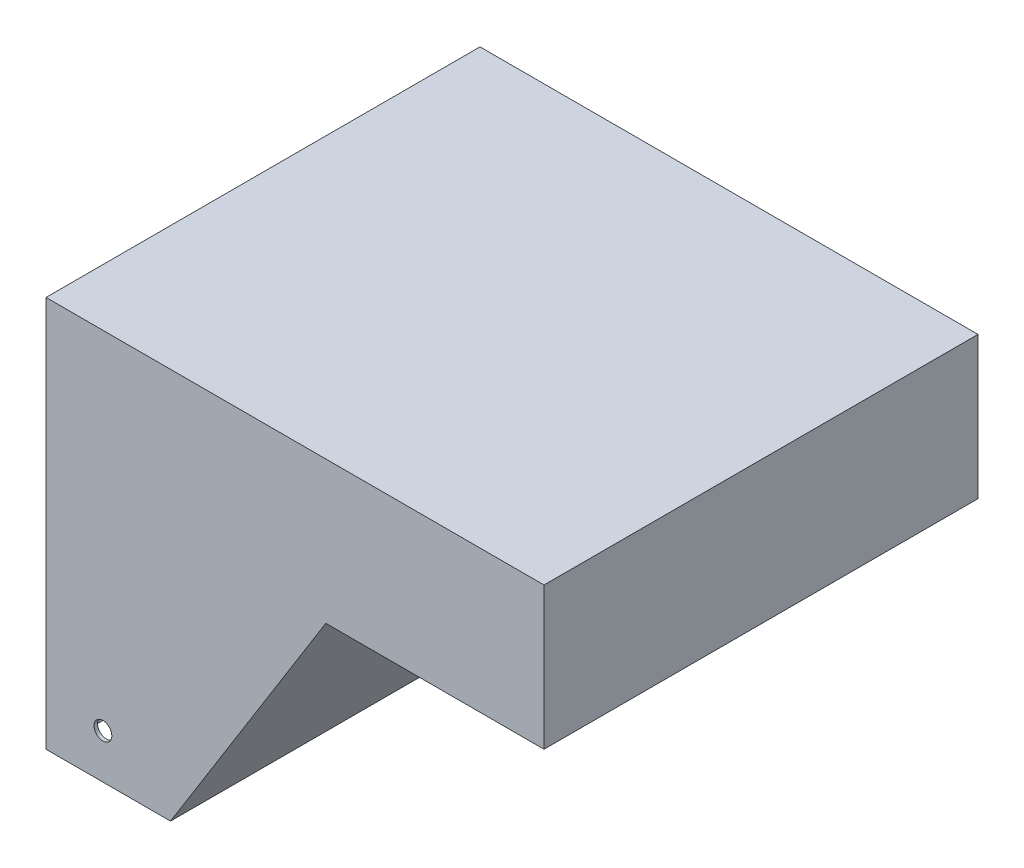
SolidWorks part; units mm, degrees
material "Acrylic (Medium-high impact)"
ref_plane "Front Plane" through (0, 0, 0) normal (0, 0, 1) x (1, 0, 0)
ref_plane "Top Plane" through (0, 0, 0) normal (0, 1, 0) x (1, 0, 0)
ref_plane "Right Plane" through (0, 0, 0) normal (1, 0, 0) x (0, 0, -1)
sketch "Sketch2" plane through (0, 0, 0) normal (0, 0, 1) x (1, 0, 0)
  line L0 (0, 0) -> (355.6, 0)
  line L1 (355.6, 0) -> (355.6, -101.6)
  line L2 (355.6, -101.6) -> (199.8078, -101.6)
  line L3 (199.8078, -101.6) -> (88.9, -279.4)
  line L4 (88.9, -279.4) -> (0, -279.4)
  line L5 (0, -279.4) -> (0, 0)
  circle A0 centre (40.64, -247.65) radius 6.35
  dimension "D6" = 12.7
  dimension "D1" = 355.6
  dimension "D2" = 279.4
  dimension "D3" = 101.6
  dimension "D4" = 88.9
  dimension "D5" = 31.75
  dimension "D7" = 40.64
extrude "Boss-Extrude1" add sketch "Sketch2" along normal blind 2.54
sketch "Sketch3" plane through (0, 0, 2.54) normal (0, 0, 1) x (1, 0, 0)
  line L6 (2.54, -276.86) -> (2.54, -279.4)
  line L7 (0, -279.4) -> (88.9, -279.4) construction
  line L8 (87.4908, -276.86) -> (87.4908, -279.4)
  line L12 (2.54, -2.54) -> (2.54, -276.86)
  line L13 (2.54, -276.86) -> (87.4908, -276.86)
  line L14 (87.4908, -276.86) -> (198.3986, -99.06)
  line L15 (198.3986, -99.06) -> (353.06, -99.06)
  line L16 (353.06, -99.06) -> (353.06, -2.54)
  line L17 (353.06, -2.54) -> (2.54, -2.54)
  line L18 (2.54, -2.54) -> (2.54, -276.86)
  line L20 (87.4908, -276.86) -> (198.3986, -99.06)
  line L21 (198.3986, -99.06) -> (353.06, -99.06)
  line L22 (353.06, -99.06) -> (353.06, -2.54)
  line L23 (353.06, -2.54) -> (2.54, -2.54)
  line M7 (0, 0) -> (0, -279.4)
  line M8 (0, -279.4) -> (88.9, -279.4)
  line M9 (88.9, -279.4) -> (199.8078, -101.6)
  line M10 (199.8078, -101.6) -> (355.6, -101.6)
  line M11 (355.6, -101.6) -> (355.6, 0)
  line M12 (355.6, 0) -> (0, 0)
  dimension "D1" = 2.54
extrude "Boss-Extrude2" add sketch "Sketch3" along normal blind 304.8 contours L23 L22 L21 L20 L18 M12 M7 M8 M9 M10 M11 region at (2.0878, -278.13, 2.54)
ref_plane "Plane1" through (0, 0, 154.94) normal (0, 0, 1) x (1, 0, 0)
mirror "Mirror1" about plane through (0, 0, 154.94) normal (0, 0, 1) of "Boss-Extrude1"
sketch "Sketch4" plane through (0, 0, 0) normal (-1, 0, 0) x (0, 0, 1)
  line L0 (309.88, -279.4) -> (0, -279.4) construction
  line L1 (120.015, -244.851) -> (189.865, -244.851) construction
  circle A0 centre (120.015, -244.851) radius 1.5875
  circle A1 centre (120.015, -270.251) radius 1.5875
  circle A2 centre (189.865, -244.851) radius 1.5875
  circle A3 centre (189.865, -270.251) radius 1.5875
  point P8 (154.94, -279.4)
  point P9 (154.94, -244.851)
  dimension "D1" = 3.175
  dimension "D2" = 69.85
  dimension "D3" = 25.4
extrude "Cut-Extrude1" cut sketch "Sketch4" against normal up to next
sketch "Sketch5" plane through (0, 0, 0) normal (0, 1, 0) x (1, 0, 0)
  line L0 (355.6, -309.88) -> (355.6, 0) construction
  line L1 (2.54, -2.54) -> (353.06, -2.54)
  line L2 (2.54, -2.54) -> (2.54, -307.34)
  line L3 (2.54, -307.34) -> (353.06, -307.34)
  line L4 (353.06, -2.54) -> (353.06, -307.34)
  line L5 (355.6, -309.88) -> (0, -309.88) construction
  line L6 (355.6, 0) -> (0, 0) construction
  line L7 (0, -309.88) -> (0, 0) construction
  dimension "D1" = 2.54
  dimension "D2" = 2.54
  dimension "D3" = 2.54
  dimension "D4" = 2.54
